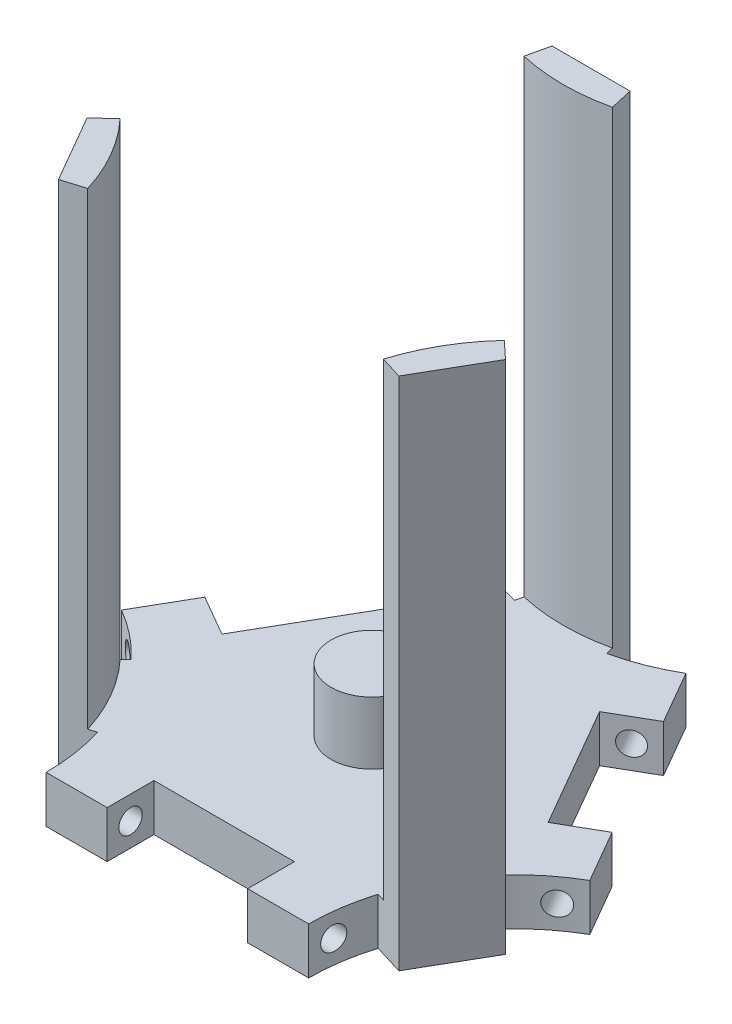
SolidWorks part; units mm, degrees
ref_plane "Front Plane" through (0, 0, 0) normal (0, 0, 1) x (1, 0, 0)
ref_plane "Top Plane" through (0, 0, 0) normal (0, 1, 0) x (1, 0, 0)
ref_plane "Right Plane" through (0, 0, 0) normal (1, 0, 0) x (0, 0, -1)
sketch "Sketch1" plane through (0, 0, 0) normal (0, 1, 0) x (1, 0, 0)
  line L0 (0, 0) -> (43.1834, 0) construction
  line L1 (43.1834, 0) -> (21.5917, 37.3979) construction
  line L2 (21.5917, 37.3979) -> (0, 0) construction
  line L3 (6.5917, 11.4171) -> (15, 25.9808)
  line L4 (28.1834, 25.9808) -> (36.5917, 11.4171)
  line L5 (13.1834, 0) -> (30, 0)
  line L6 (10.7958, 18.6989) -> (21.5917, 12.466) construction
  line L7 (21.5917, 12.466) -> (32.3875, 18.6989) construction
  line L8 (21.5917, 12.466) -> (21.5917, 0) construction
  line L9 (0, 0) -> (21.5917, 12.466) construction
  line L10 (21.5917, 12.466) -> (43.1834, 0) construction
  line L11 (21.5917, 12.466) -> (21.5917, 37.3979) construction
  line L12 (9.6546, 8.9769) -> (8.1898, 7.6152)
  line L13 (12.6016, 3.8727) -> (10.6898, 3.285)
  line L14 (8.1898, 7.6152) -> (10.6898, 3.285)
  line L15 (33.5287, 8.9769) -> (34.9935, 7.6152)
  line L16 (30.5818, 3.8727) -> (32.4935, 3.285)
  line L17 (34.9935, 7.6152) -> (32.4935, 3.285)
  line L18 (18.6448, 24.5483) -> (19.0917, 26.4977)
  line L19 (24.5386, 24.5483) -> (24.0917, 26.4977)
  line L20 (19.0917, 26.4977) -> (24.0917, 26.4977)
  arc A3 (6.5917, 11.4171) -> (9.6546, 8.9769) centre (0.0017, 0.0029) cw
  arc A4 (13.1834, 0) -> (12.6016, 3.8727) centre (0.0034, 0) ccw
  arc A5 (36.5917, 11.4171) -> (33.5287, 8.9769) centre (43.1817, 0.0029) ccw
  arc A6 (30, 0) -> (30.5818, 3.8727) centre (43.18, 0) cw
  arc A7 (15, 25.9808) -> (18.6448, 24.5483) centre (21.59, 37.395) ccw
  arc A8 (28.1834, 25.9808) -> (24.5386, 24.5483) centre (21.5934, 37.395) cw
  point P9 (10.7958, 18.6989)
  point P10 (10.7958, 18.6989)
  point P11 (32.3875, 18.6989)
  point P12 (32.3875, 18.6989)
  point P13 (21.5917, 0)
  point P15 (21.5917, 0)
  point P18 (9.4398, 5.4501)
  point P33 (33.7435, 5.4501)
  point P39 (21.5917, 26.4977)
  dimension "D2" = 13.18
  dimension "D4" = 13.18
  dimension "D5" = 13.18
  dimension "D9" = 13.18
  dimension "D10" = 13.18
  dimension "D14" = 13.18
  dimension "D1" = 30
  dimension "D3" = 16.8166
  dimension "D6" = 2
  dimension "D7" = 2
  dimension "D8" = 5
  dimension "D11" = 2
  dimension "D12" = 2
  dimension "D13" = 5
  dimension "D15" = 2
  dimension "D16" = 2
  dimension "D17" = 60
  dimension "D18" = 5
extrude "Boss-Extrude1" add sketch "Sketch1" along normal blind 3 contours L4 A5 L15 L17 L16 A6 L5 A4 L13 L14 L12 A3 L3 A7 L18 L20 L19 A8
sketch "Sketch2" plane through (0, 3, 0) normal (0, 1, 0) x (1, 0, 0)
  line L0 (21.5917, 0) -> (21.5917, 12.466) construction
  line L1 (13.1834, 0) -> (30, 0) construction
  line L2 (10.7958, 18.6989) -> (21.5917, 12.466) construction
  line L3 (6.5917, 11.4171) -> (15, 25.9808) construction
  line L4 (21.5917, 12.466) -> (32.3875, 18.6989) construction
  line L5 (28.1834, 25.9808) -> (36.5917, 11.4171) construction
  circle A0 centre (21.5917, 12.466) radius 2.625
  dimension "D1" = 5.25
extrude "Boss-Extrude2" add sketch "Sketch2" along normal blind 4
sketch "Sketch3" plane through (0, 0, 0) normal (0, -1, 0) x (1, 0, 0)
  line L0 (17.0917, 0) -> (17.0917, -3)
  line L1 (13.1834, 0) -> (30, 0) construction
  line L2 (17.0917, -3) -> (26.0917, -3)
  line L3 (26.0917, -3) -> (26.0917, 0)
  line L4 (26.0917, 0) -> (17.0917, 0)
  line L5 (6.5917, -11.4171) -> (8.5458, -14.8018) construction
  line L6 (13.0458, -22.5961) -> (15, -25.9808) construction
  line L7 (8.5458, -14.8018) -> (13.0458, -22.5961)
  line L8 (6.5917, -11.4171) -> (15, -25.9808) construction
  line L9 (13.0458, -22.5961) -> (15.6439, -21.0961)
  line L10 (15.6439, -21.0961) -> (11.1439, -13.3018)
  line L11 (11.1439, -13.3018) -> (8.5458, -14.8018)
  line L12 (28.1834, -25.9808) -> (30.1375, -22.5961) construction
  line L13 (34.6375, -14.8018) -> (36.5917, -11.4171) construction
  line L14 (34.6375, -14.8018) -> (32.0394, -13.3018)
  line L15 (28.1834, -25.9808) -> (36.5917, -11.4171) construction
  line L16 (32.0394, -13.3018) -> (27.5394, -21.0961)
  line L17 (27.5394, -21.0961) -> (30.1375, -22.5961)
  line L18 (30.1375, -22.5961) -> (34.6375, -14.8018)
  line L19 (17.0917, 0) -> (13.1834, 0) construction
  line L20 (26.0917, 0) -> (30, 0) construction
  dimension "D1" = 9
  dimension "D2" = 3
  dimension "D3" = 9
  dimension "D4" = 3
  dimension "D5" = 9
  dimension "D6" = 3
extrude "Cut-Extrude1" cut sketch "Sketch3" against normal through all
sketch "Sketch4" plane through (2.25, 0, 3.8971) normal (-0.5, 0, -0.866) x (-0.866, 0, 0.5)
  line L0 (-34.3979, 3) -> (-37.3979, 3) construction
  line L1 (-37.3979, 3) -> (-37.3979, 0) construction
  circle A0 centre (-35.8979, 1.5) radius 0.75
  dimension "D1" = 1.5
  dimension "D2" = 1.5
  dimension "D3" = 1.5
extrude "Cut-Extrude2" cut sketch "Sketch4" against normal through all and the other way through all
sketch "Sketch5" plane through (8.5458, 0, -14.8018) normal (0.5, 0, -0.866) x (-0.866, 0, -0.5)
  line L0 (-3, 0) -> (0, 0) construction
  line L1 (0, 3) -> (0, 0) construction
  circle A0 centre (-1.5, 1.5) radius 0.75
  dimension "D1" = 1.5
  dimension "D2" = 1.5
  dimension "D3" = 1.5
extrude "Cut-Extrude3" cut sketch "Sketch5" against normal through all and the other way through all
sketch "Sketch6" plane through (26.0917, 0, 0) normal (-1, 0, 0) x (0, 0, 1)
  line L0 (0, 3) -> (-3, 3) construction
  line L1 (0, 3) -> (0, 0) construction
  circle A0 centre (-1.5, 1.5) radius 0.75
  dimension "D1" = 1.5
  dimension "D2" = 1.5
  dimension "D3" = 1.5
extrude "Cut-Extrude4" cut sketch "Sketch6" against normal through all and the other way through all
sketch "Sketch7" plane through (0, 3, 0) normal (0, 1, 0) x (1, 0, 0)
  line L1 (8.1898, 7.6152) -> (10.6898, 3.285)
  line L4 (32.4935, 3.285) -> (34.9935, 7.6152)
  line L7 (19.0917, 26.4977) -> (24.0917, 26.4977)
  line L9 (19.0917, 26.4977) -> (18.7565, 25.0356)
  line L10 (18.6448, 24.5483) -> (19.0917, 26.4977) construction
  line L11 (24.0917, 26.4977) -> (24.4269, 25.0356)
  line L12 (24.5386, 24.5483) -> (24.0917, 26.4977) construction
  line L13 (8.1898, 7.6152) -> (9.2884, 8.6365)
  line L14 (9.6546, 8.9769) -> (8.1898, 7.6152) construction
  line L15 (10.6898, 3.285) -> (12.1236, 3.7258)
  line L16 (12.6016, 3.8727) -> (10.6898, 3.285) construction
  line L17 (34.9935, 7.6152) -> (33.8949, 8.6365)
  line L18 (33.5287, 8.9769) -> (34.9935, 7.6152) construction
  line L19 (32.4935, 3.285) -> (31.0597, 3.7258)
  line L20 (30.5818, 3.8727) -> (32.4935, 3.285) construction
  arc A3 (18.7565, 25.0356) -> (24.4269, 25.0356) centre (21.5917, 37.4023) ccw
  arc A4 (33.8949, 8.6365) -> (31.0597, 3.7258) centre (43.1872, -0.0022) ccw
  arc A5 (9.2884, 8.6365) -> (12.1236, 3.7258) centre (-0.0038, -0.0022) cw
  dimension "D1" = 1.5
  dimension "D2" = 1.5
  dimension "D3" = 1.5
  dimension "D4" = 1.5
  dimension "D5" = 1.5
  dimension "D6" = 1.5
extrude "Boss-Extrude3" add sketch "Sketch7" along normal blind 30
